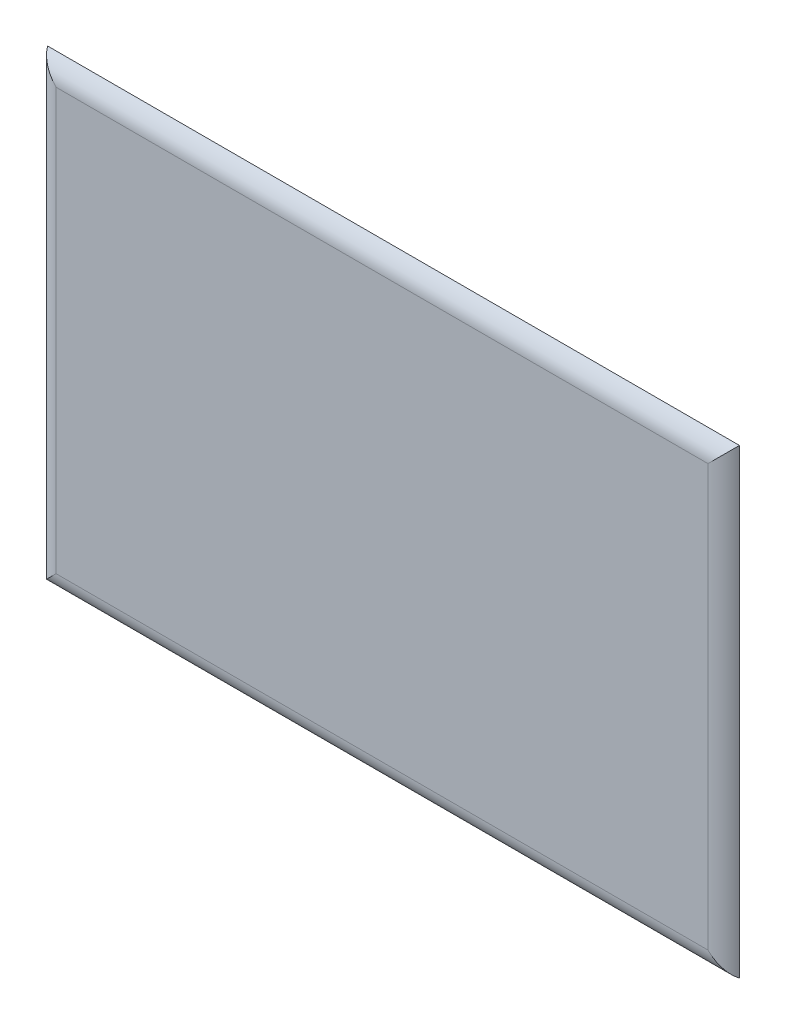
SolidWorks part; units mm, degrees
ref_plane "Front Plane" through (0, 0, 0) normal (0, 0, 1) x (1, 0, 0)
ref_plane "Top Plane" through (0, 0, 0) normal (0, 1, 0) x (1, 0, 0)
ref_plane "Right Plane" through (0, 0, 0) normal (1, 0, 0) x (0, 0, -1)
sketch "Sketch1" plane through (0, 0, 0) normal (0, 0, 1) x (1, 0, 0)
  line L1 (-97.6493, 27.1545) -> (202.3507, 27.1545)
  line L2 (-97.6493, 27.1545) -> (-97.6493, -172.8455)
  line L3 (-97.6493, -172.8455) -> (202.3507, -172.8455)
  line L4 (202.3507, 27.1545) -> (202.3507, -172.8455)
  dimension "D1" = 300
  dimension "D2" = 200
extrude "Boss-Extrude1" add sketch "Sketch1" along normal blind 5
fillet "Fillet1" radius 10 4 edges at (-97.6493, -72.8455, 5) (52.3507, -172.8455, 5) (202.3507, -72.8455, 5) (52.3507, 27.1545, 5)
